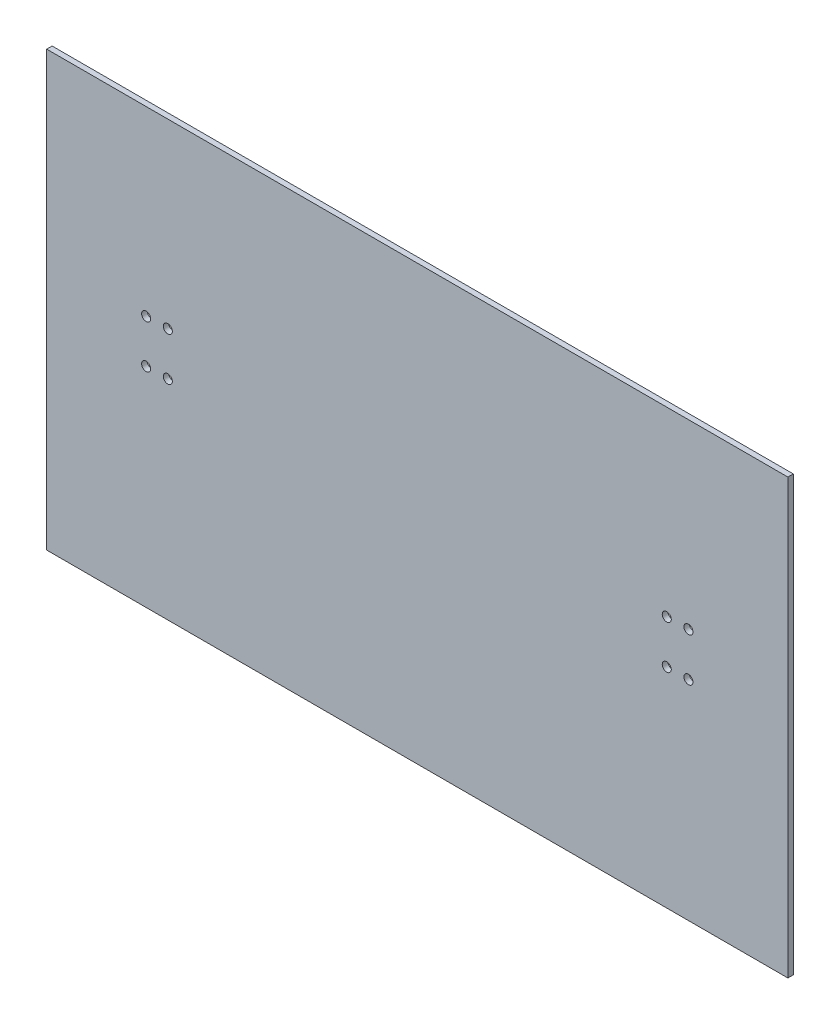
SolidWorks part; units mm, degrees
material "Acrylic (Medium-high impact)"
ref_plane "Front Plane" through (0, 0, 0) normal (0, 0, 1) x (1, 0, 0)
ref_plane "Top Plane" through (0, 0, 0) normal (0, 1, 0) x (1, 0, 0)
ref_plane "Right Plane" through (0, 0, 0) normal (1, 0, 0) x (0, 0, -1)
sketch "Sketch1" plane through (0, 0, 0) normal (0, 0, 1) x (1, 0, 0)
  line L1 (-205, -120) -> (205, -120)
  line L2 (-205, -120) -> (-205, 120)
  line L3 (-205, 120) -> (205, 120)
  line L4 (205, -120) -> (205, 120)
  line L5 (-205, -120) -> (205, 120) construction
  line L6 (-205, 120) -> (205, -120) construction
  point P0 (0, 0)
  dimension "D1" = 240
  dimension "D2" = 410
extrude "Boss-Extrude1" add sketch "Sketch1" along normal mid plane 3
sketch "Sketch2" plane through (0, 0, -1.5) normal (0, 0, -1) x (-1, 0, 0)
  line L0 (205, 120) -> (205, -120) construction
  line L1 (-205, -120) -> (-205, 120) construction
  line L3 (205, -120) -> (-205, -120) construction
  circle A8 centre (150, 19.5277) radius 2.5
  circle A9 centre (138, 19.5277) radius 2.5
  circle A10 centre (138, -4.4723) radius 2.5
  circle A11 centre (150, -4.4723) radius 2.5
  circle A12 centre (-150, 19.5277) radius 2.5
  circle A13 centre (-138, 19.5277) radius 2.5
  circle A14 centre (-138, -4.4723) radius 2.5
  circle A15 centre (-150, -4.4723) radius 2.5
  point P1 (0, 0)
  point P3 (0, 0)
  point P9 (0, 0)
  point P11 (0, 0)
  point P13 (0, 0)
  point P24 (0, 0)
  point P26 (0, 0)
  point P29 (0, 0)
  point P30 (0, 0)
  point P31 (138, -4.4723)
  point P32 (138, 19.5277)
  point P33 (150, -15.2447)
  point P34 (138, -4.4723)
  point P35 (138, -4.4723)
  point P36 (138, 19.5277)
  point P37 (150, 15.5204)
  dimension "D1" = 55
  dimension "D2" = 115.5277
  dimension "D3" = 24
  dimension "D4" = 12
  dimension "D5" = 5
  dimension "D6" = 12
  dimension "D7" = 55
extrude "Cut-Extrude1" cut sketch "Sketch2" against normal through all
